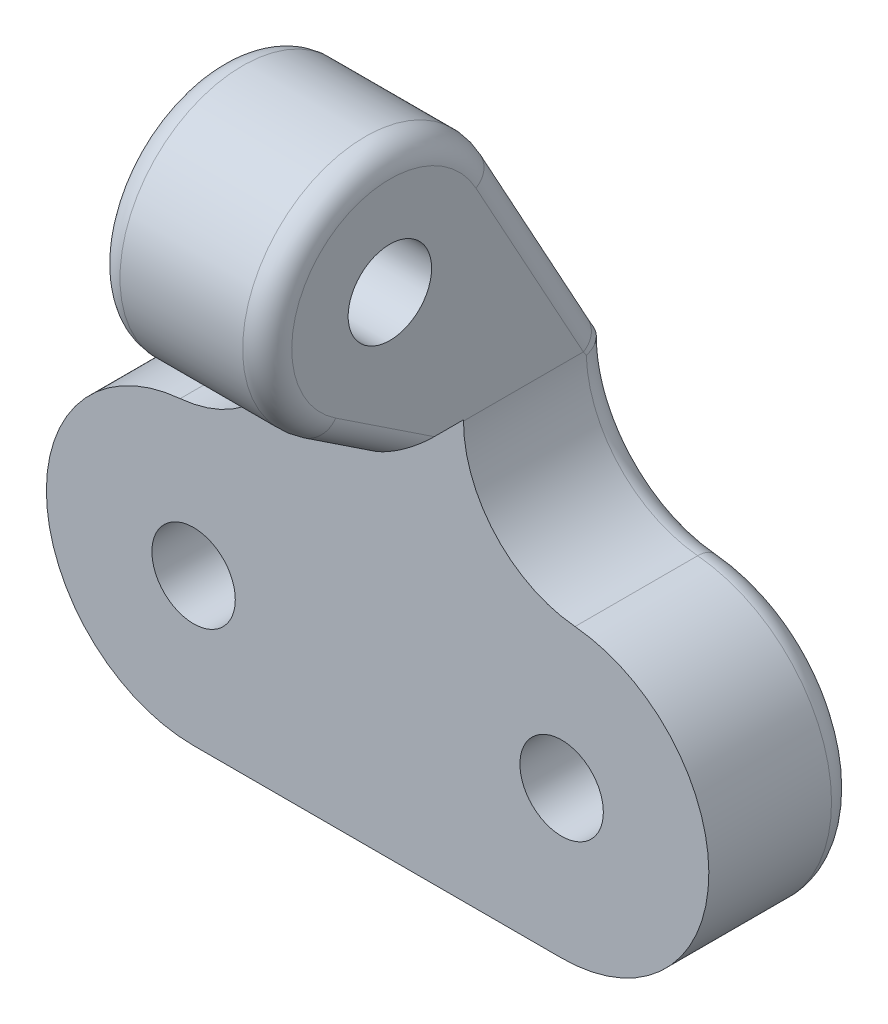
SolidWorks part; units mm, degrees
ref_plane "Plan de face" through (0, 0, 0) normal (0, 0, 1) x (1, 0, 0)
ref_plane "Plan de dessus" through (0, 0, 0) normal (0, 1, 0) x (1, 0, 0)
ref_plane "Plan de droite" through (0, 0, 0) normal (1, 0, 0) x (0, 0, -1)
sketch "Esquisse1" plane through (0, 0, 0) normal (0, 0, 1) x (1, 0, 0)
  line L0 (7.5, 0) -> (-7.5, 0) construction
  line L1 (-7.5, 0) -> (7.5, 0) construction
  line L2 (-7.5, 6) -> (7.5, 6)
  line L3 (-7.5, -6) -> (7.5, -6)
  circle A0 centre (-7.5, 0) radius 1.7
  circle A1 centre (7.5, 0) radius 1.7
  arc A2 (-7.5, 6) -> (-7.5, -6) centre (-7.5, 0) ccw
  arc A3 (7.5, -6) -> (7.5, 6) centre (7.5, 0) ccw
  point P4 (0, 0)
  point P7 (0, 0)
  dimension "D1" = 3.4
  dimension "D3" = 6
  dimension "D2" = 15
extrude "Boss.-Extru.1" add sketch "Esquisse1" along normal blind 6
sketch "Esquisse2" plane through (0, 0, 0) normal (1, 0, 0) x (0, 0, -1)
  line L0 (-9, 17) -> (-9, 11) construction
  line L1 (-6, 6) -> (0, 6)
  line L2 (-6, 6) -> (-6, 11)
  line L3 (-6, 11) -> (0, 11) construction
  line L4 (0, 6) -> (0, 11)
  line L5 (-9, 11) -> (-6, 11)
  line L6 (-9, 11) -> (-11.7639, 12.8333)
  line L7 (-4.6175, 19.407) -> (0, 11)
  circle A0 centre (-9, 17) radius 5 construction
  circle A1 centre (-9, 17) radius 1.7
  arc A2 (-4.6175, 19.407) -> (-11.7639, 12.8333) centre (-9, 17) ccw
  dimension "D1" = 10
  dimension "D2" = 3.4
  dimension "D3" = 5
  dimension "D4" = 6
  dimension "D5" = 3
extrude "Boss.-Extru.2" add sketch "Esquisse2" along normal mid plane 7
fillet "Congé1" radius 5 2 edges at (-3.5, 6, 3) (3.5, 6, 3)
fillet "Congé2" radius 1 13 edges at (-3.5, 11.9167, 10.3819) (-3.5, 20.6799, 12.385) (3.5, 11.9167, 10.3819) (3.5, 20.6799, 12.385) (-4.8073, 7.5835, 0) (-13.4938, -0.273, 0) (0, -6, 0) (4.8073, 7.5835, 0) (-3.5, 15.2035, 2.3088) (3.5, 15.2035, 2.3088) (13.4938, -0.273, 0) (-3.5, 10.9772, 0) (3.5, 10.9772, 0)
sketch "Esquisse3" plane through (0, 0, 0) normal (0, 0, -1) x (-1, 0, 0)
  line L0 (-9.1454, 2.85) -> (-5.8546, 2.85)
  line L1 (-5.8546, 2.85) -> (-4.2091, 0)
  line L2 (-4.2091, 0) -> (-5.8546, -2.85)
  line L3 (-5.8546, -2.85) -> (-9.1454, -2.85)
  line L4 (-9.1454, -2.85) -> (-10.7909, 0)
  line L5 (-10.7909, 0) -> (-9.1454, 2.85)
  line L6 (-10.7909, 0) -> (-4.2091, 0) construction
  line L7 (5.8546, 2.85) -> (9.1454, 2.85)
  line L8 (9.1454, 2.85) -> (10.7909, 0)
  line L9 (10.7909, 0) -> (9.1454, -2.85)
  line L10 (9.1454, -2.85) -> (5.8546, -2.85)
  line L11 (5.8546, -2.85) -> (4.2091, 0)
  line L12 (4.2091, 0) -> (5.8546, 2.85)
  line L13 (4.2091, 0) -> (10.7909, 0) construction
  point P2 (7.5, 0)
  point P13 (-7.5, 0)
  point P14 (-7.5, 0)
  point P17 (7.5, 0)
  point P18 (-9.1454, -2.85)
  dimension "D1" = 120
  dimension "D2" = 5.7
  dimension "D3" = 120
  dimension "D4" = 5.7
extrude "Enlèv. mat.-Extru.1" cut sketch "Esquisse3" against normal blind 3
